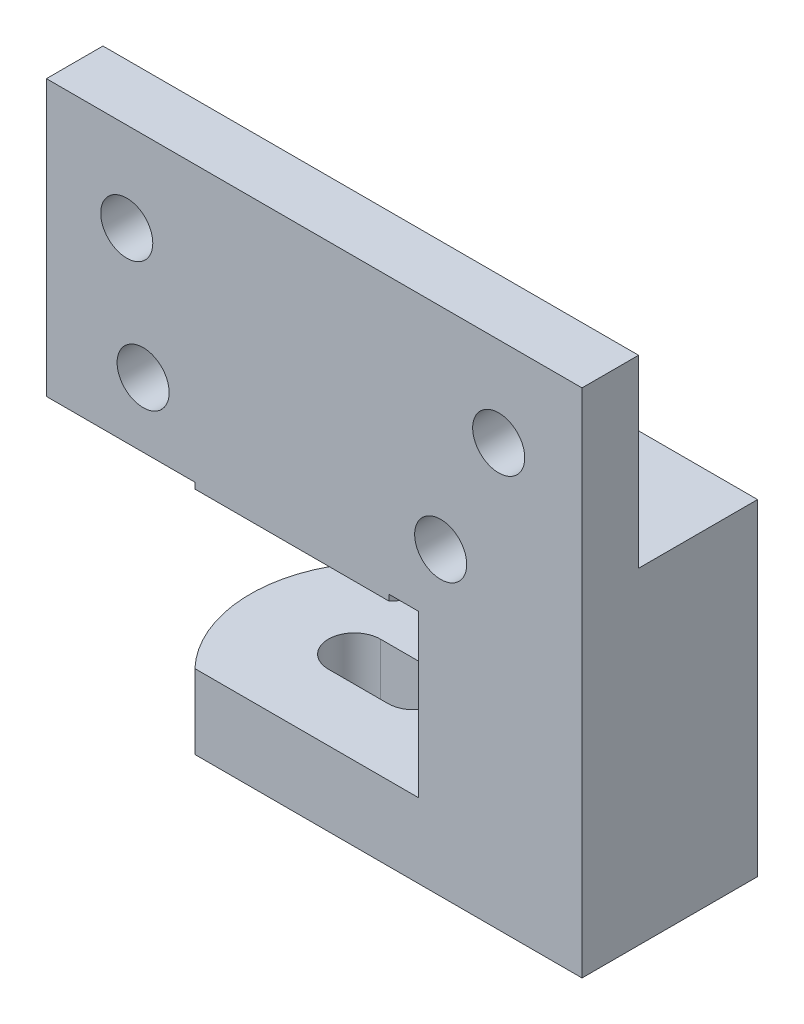
SolidWorks part; units mm, degrees
note: The reader was unsure of these and kept them because the rebuilt part matched: shared geometry of "Croquis7<3>".
ref_plane "Front Plane" through (0, 0, 0) normal (0, 0, 1) x (1, 0, 0)
ref_plane "Top Plane" through (0, 0, 0) normal (0, 1, 0) x (1, 0, 0)
ref_plane "Right Plane" through (0, 0, 0) normal (1, 0, 0) x (0, 0, -1)
sketch "Croquis2" plane through (0, 0, 0) normal (0, 0, 1) x (1, 0, 0)
  line L0 (-10.65, -27.2) -> (-52.65, -27.2) construction
  line L1 (-52.65, -21.1) -> (-19.65, -21.1)
  line L6 (-52.65, -21.1) -> (-52.65, -27.2)
  line L7 (-45.15, -28.05) -> (-27.15, -28.05) construction
  line L8 (-45.15, -28.05) -> (-27.15, -28.05) construction
  line L10 (-52.65, -21.1) -> (-19.65, -21.1) construction
  line L11 (-52.65, -8.55) -> (-52.65, -27.2) construction
  line L12 (-360.25, -20.7) -> (-10.25, -20.7) construction
  line L13 (-19.65, -21.1) -> (-19.65, -27.2)
  line L14 (-52.65, -27.2) -> (-19.65, -27.2)
  dimension "D1" = 33
  dimension "D2" = 0.4
extrude "Saliente-Extruir2" add sketch "Croquis2" along normal offset from surface (11.8 mm away) 4 from offset 0.2 offset beyond the face yes
sketch "Croquis3" plane through (0, -27.2, 0) normal (0, -1, 0) x (1, 0, 0)
  line L0 (-19.65, 12) -> (-19.65, 0.2) construction
  line L1 (-52.65, 12) -> (-19.65, 12)
  line L2 (-52.65, 12) -> (-52.65, 8.2)
  line L3 (-52.65, 8.2) -> (-19.65, 8.2)
  line L4 (-19.65, 12) -> (-19.65, 8.2)
  line L6 (-360.25, 8) -> (-10.25, 8) construction
  circle A0 centre (-36.15, 5.7981) radius 9 construction
  circle A1 centre (-36.15, 5.7981) radius 9
  line M2 (-19.65, 0.2) -> (-19.65, 12)
  line M3 (-19.65, 12) -> (-52.65, 12)
  line M4 (-52.65, 12) -> (-52.65, 0.2)
  dimension "D1" = 0.2
extrude "Saliente-Extruir3" add sketch "Croquis3" against normal up to surface (18.5 mm away) contours A1 L3 M3 M4 | A1 L3 M2 M3 | L3 A1 L1
sketch "Croquis4" plane through (0, -27.2, 0) normal (0, -1, 0) x (1, 0, 0)
  line L0 (-19.65, 12) -> (-52.65, 12) construction
  line L1 (-19.65, 12) -> (-52.65, 12)
  line L2 (-52.65, 0.2) -> (-19.65, 0.2) construction
  line L3 (-52.65, 0.2) -> (-19.65, 0.2)
  circle A0 centre (-36.15, 5.7981) radius 9 construction
  circle A1 centre (-36.15, 5.7981) radius 9
extrude "Saliente-Extruir5" add sketch "Croquis4" along normal blind 0.4 contours L1 A1 L3
sketch "Croquis6" plane through (-19.65, 0, 0) normal (1, 0, 0) x (0, 0, -1)
  line L6 (-0.2, -21.1) -> (-8.2, -21.1)
  line L7 (-8.2, -21.1) -> (-8.2, -8.7)
  line L8 (-8.2, -8.7) -> (-12, -8.7)
  line L9 (-12, -8.7) -> (-12, -27.2)
  line L10 (-12, -27.2) -> (-0.2, -27.2)
  line L11 (-0.2, -27.2) -> (-0.2, -21.1)
  line L12 (-0.2, -21.1) -> (-8.2, -21.1)
  line L13 (-8.2, -21.1) -> (-8.2, -8.7)
  line L14 (-8.2, -8.7) -> (-12, -8.7)
  line L15 (-12, -8.7) -> (-12, -27.2)
  line L16 (-12, -27.2) -> (-0.2, -27.2)
  line L17 (-0.2, -27.2) -> (-0.2, -21.1)
  dimension "D1" = 0
extrude "Saliente-Extruir6" add sketch "Croquis6" along normal blind 3
sketch "Croquis5" plane through (0, 0, 12) normal (0, 0, 1) x (1, 0, 0)
  circle A0 centre (-22.25, -14.7) radius 1.75 construction
  circle A1 centre (-22.25, -14.7) radius 1.75
  circle A2 centre (-47.25, -14.7) radius 1.75 construction
  circle A3 centre (-47.25, -14.7) radius 1.75
  circle A4 centre (-46.15, -22.85) radius 1.75 construction
  circle A5 centre (-46.15, -22.85) radius 1.75
  circle A6 centre (-26.15, -22.85) radius 1.75 construction
  circle A7 centre (-26.15, -22.85) radius 1.75
extrude "Cortar-Extruir1" cut sketch "Croquis5" against normal up to next
sketch "Croquis7" plane through (0, -27.2, 0) normal (0, -1, 0) x (1, 0, 0)
  line L0 (-45.15, 5.7981) -> (-27.15, 5.7981) construction
  line L1 (-45.15, 5.7981) -> (-27.15, 5.7981)
  line L2 (-36.15, 5.7981) -> (-36.15, 8.7981) construction
  line L3 (-41.6121, 5.7981) -> (-39.88, 2.7981)
  line L4 (-39.88, 2.7981) -> (-32.42, 2.7981)
  line L5 (-32.42, 2.7981) -> (-30.6879, 5.7981)
  line L6 (-30.6879, 5.7981) -> (-32.42, 8.7981)
  line L7 (-32.42, 8.7981) -> (-39.88, 8.7981)
  line L8 (-39.88, 8.7981) -> (-41.6121, 5.7981)
  circle A0 centre (-36.15, 5.7981) radius 1.7
  dimension "D1" = 7.46
  dimension "D2" = 3.4
  dimension "D3" = 120
  dimension "D4" = 120
  dimension "D5" = 3.4641
  dimension "D6" = 3.4641
  dimension "D7" = 3.4641
  dimension "D8" = 3.4641
extrude "Cortar-Extruir2" cut sketch "Croquis7" along normal blind 2.6 and the other way blind 3.5 from surface at -6.1 contours A0 L1 L7 L8 L3 L4 | A0 L1 L4 L5 L6 L7 | L1 A0 | L1 A0 | A0 L2 L7 L8 L1 | L1 L2 A0
extrude "Cortar-Extruir3" cut sketch "Croquis7<3>" along normal through all and the other way through all contours L1 A0 | L1 A0
sketch "Croquis7<3>" plane through (0, -27.2, 0) normal (0, -1, 0) x (1, 0, 0) same geometry as "Croquis7"
sketch "Croquis8" plane through (0, -27.2, 0) normal (0, -1, 0) x (1, 0, 0)
  line L0 (-29.1029, 0.2) -> (-16.65, 0.2) construction
  line L9 (-16.65, 12) -> (-29.6281, 12) construction
  line L12 (-29.1029, 0.2) -> (-16.65, 0.2)
  line L13 (-16.65, 0.2) -> (-16.65, 12)
  line L14 (-16.65, 12) -> (-29.6281, 12)
  line L15 (-27.2197, 0.2) -> (-16.65, 0.2)
  line L16 (-16.65, 0.2) -> (-16.65, 12)
  line L17 (-16.65, 12) -> (-27.6281, 12)
  arc A0 (-27.6281, 12) -> (-27.2197, 0.2) centre (-36.15, 5.7981) cw
  arc A4 (-29.1029, 0.2) -> (-29.6281, 12) centre (-36.15, 5.7981) ccw
  point P12 (0, 0)
  point P14 (-27.1029, 0.2)
  point P15 (-27.1791, 0.2)
  dimension "D2" = 2
  dimension "D1" = 0
extrude "Saliente-Extruir7" add sketch "Croquis8" along normal offset from surface (10.85 mm away) 1
sketch "Croquis9" plane through (0, -38.05, 0) normal (0, -1, 0) x (1, 0, 0)
  line L0 (-16.65, 12) -> (-16.65, 0.2)
  line L2 (-29.6281, 12) -> (-42.6719, 12)
  line L3 (-43.1971, 0.2) -> (-29.1029, 0.2)
  line L4 (-16.65, 12) -> (-42.6719, 12)
  line L5 (-43.1971, 0.2) -> (-16.65, 0.2)
  arc A2 (-42.6719, 12) -> (-43.1971, 0.2) centre (-36.15, 5.7981) ccw
  arc A3 (-29.1029, 0.2) -> (-29.6281, 12) centre (-36.15, 5.7981) ccw
  arc A4 (-42.6719, 12) -> (-43.1971, 0.2) centre (-36.15, 5.7981) ccw
  dimension "D1" = 0
extrude "Saliente-Extruir8" add sketch "Croquis9" along normal blind 5
sketch "Croquis10" plane through (0, -43.05, 0) normal (0, -1, 0) x (1, 0, 0)
  line L0 (-38.15, 5.7981) -> (-34.15, 5.7981) construction
  line L1 (-38.15, 7.5481) -> (-34.15, 7.5481)
  line L2 (-38.15, 4.0481) -> (-34.15, 4.0481)
  circle A0 centre (-36.15, 5.7981) radius 1.7 construction
  circle A1 centre (-36.15, 5.7981) radius 1.7 construction
  arc A2 (-38.15, 7.5481) -> (-38.15, 4.0481) centre (-38.15, 5.7981) ccw
  arc A3 (-34.15, 4.0481) -> (-34.15, 7.5481) centre (-34.15, 5.7981) ccw
  point P5 (-36.15, 5.7981)
  dimension "D1" = 3.5
  dimension "D2" = 4
extrude "Cortar-Extruir4" cut sketch "Croquis10" against normal through all
